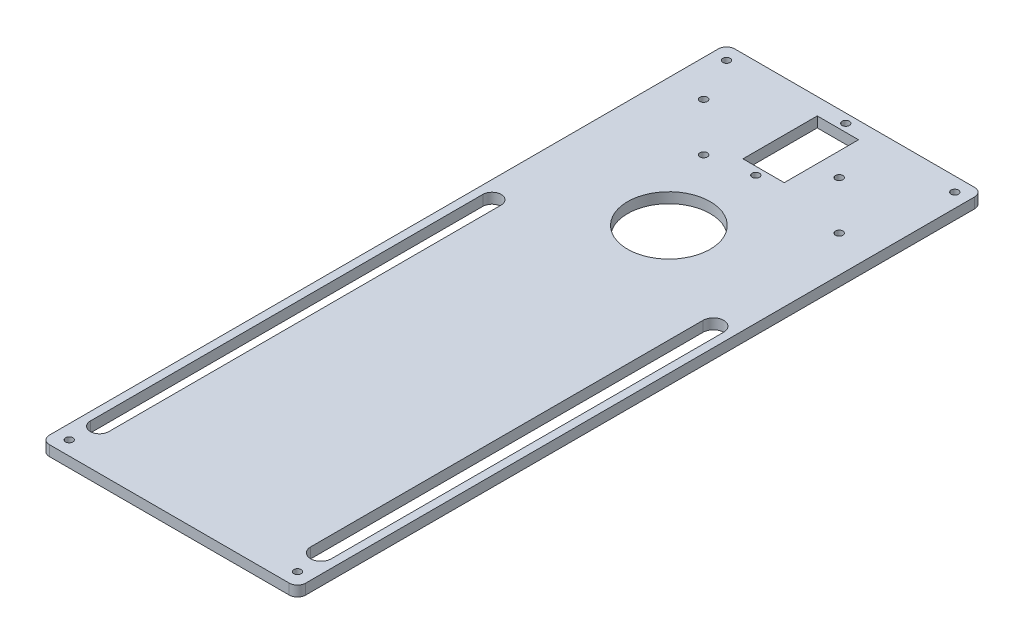
SolidWorks part; units mm, degrees
material "Brass"
ref_plane "Front Plane" through (0, 0, 0) normal (0, 0, 1) x (1, 0, 0)
ref_plane "Top Plane" through (0, 0, 0) normal (0, 1, 0) x (1, 0, 0)
ref_plane "Right Plane" through (0, 0, 0) normal (1, 0, 0) x (0, 0, -1)
sketch "Sketch2" plane through (0, 0, 0) normal (0, 0, 1) x (1, 0, 0)
  line L0 (-44.45, 0) -> (-44.45, -3.2004)
  line L1 (0, 0) -> (0, -3.2004) construction
  line L2 (-44.45, -3.2004) -> (34.3945, -3.2004)
  line L3 (34.3945, 0) -> (34.3945, -3.2004)
  line L4 (-44.45, 0) -> (34.3945, 0)
  dimension "D1" = 78.8445
  dimension "D2" = 3.2004
extrude "Boss-Extrude1" add sketch "Sketch2" along normal blind 210.82 contours L4 L3 L2 L0
sketch "Sketch3" plane through (0, -3.2004, 0) normal (0, -1, 0) x (1, 0, 0)
  line L0 (-44.45, 57.15) -> (34.3945, 57.15) construction
  line L1 (30.0765, 210.82) -> (30.0765, 206.502) construction
  line L2 (30.0765, 206.502) -> (34.3945, 206.502) construction
  line L3 (-44.45, 210.82) -> (34.3945, 210.82) construction
  line L4 (-5.0278, 57.15) -> (-5.0278, 0) construction
  line L5 (-44.45, 0) -> (34.3945, 0) construction
  line L6 (-41.91, 77.5174) -> (-36.2424, 77.5174) construction
  line L7 (-41.91, 77.5174) -> (-41.91, 198.224)
  line L8 (-41.91, 198.224) -> (-36.2424, 198.224) construction
  line L9 (-36.2424, 77.5174) -> (-36.2424, 198.224)
  line L10 (-39.0762, 210.82) -> (-39.0762, 201.0579) construction
  line L11 (-41.91, 137.8707) -> (-44.45, 137.8707) construction
  line L12 (25.5045, 77.1762) -> (31.8545, 77.1762) construction
  line L13 (25.5045, 77.1762) -> (25.5045, 197.8829)
  line L14 (25.5045, 197.8829) -> (31.8545, 197.8829) construction
  line L15 (31.8545, 77.1762) -> (31.8545, 197.8829)
  line L16 (28.6795, 210.82) -> (28.6795, 201.0579) construction
  line L17 (34.3945, 137.5296) -> (31.8545, 137.5296) construction
  line L18 (34.3945, 210.82) -> (34.3945, 0) construction
  line L19 (-44.45, 4.318) -> (-40.132, 4.318) construction
  line L20 (34.3945, 210.82) -> (34.3945, 0) construction
  line L21 (-44.45, 210.82) -> (-44.45, 0) construction
  line L22 (-44.45, 210.82) -> (-44.45, 0) construction
  line L23 (-40.132, 210.82) -> (-40.132, 206.502) construction
  line L24 (-44.45, 206.502) -> (-40.132, 206.502) construction
  line L25 (-44.45, 210.82) -> (34.3945, 210.82) construction
  line L26 (-40.132, 4.318) -> (-40.132, 0) construction
  line L27 (-44.45, 0) -> (34.3945, 0) construction
  line L28 (34.3945, 4.318) -> (30.0765, 4.318) construction
  line L29 (30.0765, 0) -> (30.0765, 4.318) construction
  line L30 (-11.3778, 28.0256) -> (-11.3778, 5.1656)
  line L31 (1.3222, 28.0256) -> (1.3222, 5.1656)
  line L32 (-11.3778, 5.1656) -> (1.3222, 5.1656)
  line L33 (-11.3778, 28.0256) -> (1.3222, 28.0256)
  line L34 (-18.4797, 33.02) -> (-33.2664, 18.2334) construction
  line L35 (23.2109, 33.02) -> (8.4242, 18.2334) construction
  line L36 (-44.45, 0) -> (34.3945, 0) construction
  line L37 (-33.2664, 18.2334) -> (-44.45, 18.2334) construction
  line L39 (34.3945, 33.02) -> (23.2109, 33.02) construction
  line L40 (23.2109, 33.02) -> (23.2109, 0) construction
  line L41 (23.2109, 33.02) -> (-18.4797, 33.02) construction
  circle A0 centre (-5.0278, 57.15) radius 12.7
  arc A1 (-41.91, 198.224) -> (-36.2424, 198.224) centre (-39.0762, 198.224) cw
  arc A2 (-36.2424, 77.5174) -> (-41.91, 77.5174) centre (-39.0762, 77.5174) cw
  arc A3 (25.5045, 197.8829) -> (31.8545, 197.8829) centre (28.6795, 197.8829) cw
  arc A4 (31.8545, 77.1762) -> (25.5045, 77.1762) centre (28.6795, 77.1762) cw
  circle A5 centre (-40.132, 206.502) radius 1.1303
  circle A6 centre (30.0765, 206.502) radius 1.1303
  circle A7 centre (-40.132, 4.318) radius 1.1303
  circle A8 centre (30.0765, 4.318) radius 1.1303
  circle A9 centre (-5.0278, 30.4259) radius 1.1303
  circle A10 centre (-5.0278, 2.7653) radius 1.1303
  circle A11 centre (23.2109, 33.02) radius 1.143
  circle A12 centre (8.4242, 18.2334) radius 1.143
  circle A13 centre (-18.4797, 33.02) radius 1.143
  circle A14 centre (-33.2664, 18.2334) radius 1.143
  point P53 (-5.0278, 28.0256)
  point P58 (-5.0278, 28.0256)
  point P67 (-5.0278, 5.1656)
  dimension "D1" = 25.4
  dimension "D11" = 2.2606
  dimension "D15" = 2.2606
  dimension "D16" = 2.7653
  dimension "D18" = 2.4003
  dimension "D19" = 45
  dimension "D25" = 2.286
  dimension "D2" = 57.15
  dimension "D3" = 120.7066
  dimension "D4" = 5.6676
  dimension "D5" = 9.7621
  dimension "D6" = 2.54
  dimension "D7" = 120.7066
  dimension "D8" = 6.35
  dimension "D9" = 9.7621
  dimension "D10" = 2.54
  dimension "D12" = 4.318
  dimension "D13" = 22.86
  dimension "D14" = 12.7
  dimension "D17" = 2.4003
  dimension "D20" = 11.1836
  dimension "D23" = 33.02
  dimension "D26" = 11.1836
  dimension "D27" = 20.9115
extrude "Cut-Extrude1" cut sketch "Sketch3" against normal through all
fillet "Fillet1" radius 2.54 4 edges at (34.3945, -1.6002, 210.82) (-44.45, -1.6002, 210.82) (-44.45, -1.6002, 0) (34.3945, -1.6002, 0)
sketch "Sketch4" plane through (0, 0, 210.82) normal (0, 0, 1) x (1, 0, 0)
  line L0 (-5.0278, 0) -> (-5.0278, -3.2004) construction
  line L1 (-44.45, 0) -> (34.3945, 0) construction
  line L2 (-44.45, -3.2004) -> (34.3945, -3.2004) construction
sketch "Sketch6" plane through (34.3945, 0, 0) normal (1, 0, 0) x (0, 0, -1)
  line L0 (-105.41, 0) -> (-105.41, -3.2004) construction
  line L3 (-210.82, -3.2004) -> (0, -3.2004) construction
  line L4 (-210.82, 0) -> (0, 0) construction
